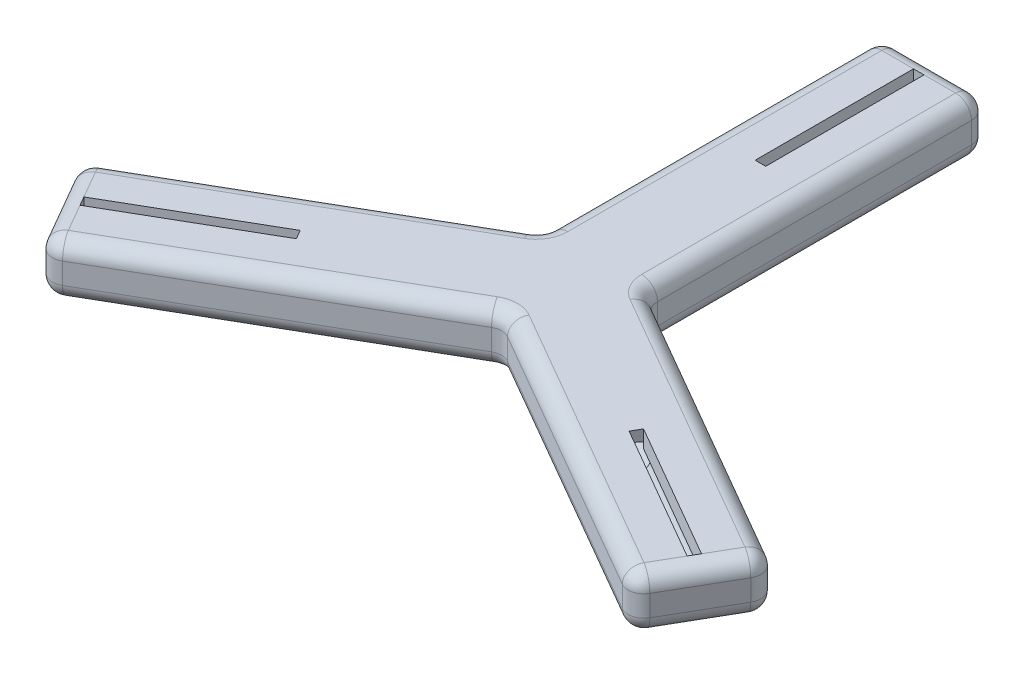
SolidWorks part; units mm, degrees
ref_plane "Front Plane" through (0, 0, 0) normal (0, 0, 1) x (1, 0, 0)
ref_plane "Top Plane" through (0, 0, 0) normal (0, 1, 0) x (1, 0, 0)
ref_plane "Right Plane" through (0, 0, 0) normal (1, 0, 0) x (0, 0, -1)
sketch "Sketch2" plane through (0, 0, 0) normal (0, 1, 0) x (1, 0, 0)
  line L3 (10, 5.7735) -> (10, 70)
  line L4 (-10, 5.7735) -> (-65.6218, -26.3397)
  line L5 (0, -11.547) -> (55.6218, -43.6603)
  line L6 (-10, 5.7735) -> (-10, 70)
  line L7 (0, -11.547) -> (-55.6218, -43.6603)
  line L8 (10, 5.7735) -> (65.6218, -26.3397)
  line L9 (-10, 70) -> (10, 70)
  line L10 (65.6218, -26.3397) -> (55.6218, -43.6603)
  line L11 (-65.6218, -26.3397) -> (-55.6218, -43.6603)
extrude "Boss-Extrude1" add sketch "Sketch2" along normal blind 10
ref_plane "Plane1" through (-2.5, 0, -4.3301) normal (-0.5, 0, -0.866) x (-0.866, 0, 0.5)
ref_plane "Plane2" through (0, 0, 0) normal (-0.5, 0, -0.866) x (-0.866, 0, 0.5)
fillet "Fillet3" radius 3 27 edges at (-10, 5, -70) (10, 5, -70) (65.6218, 5, 26.3397) (55.6218, 5, 43.6603) (-65.6218, 5, 26.3397) (-55.6218, 5, 43.6603) (10, 10, -37.8868) (10, 5, -5.7735) (37.8109, 0, 10.2831) (10, 0, -37.8868) (60.6218, 0, 35) (60.6218, 10, 35) (27.8109, 0, 27.6036) (0, 5, 11.547) (-27.8109, 0, 27.6036) (-10, 5, -5.7735) (-37.8109, 0, 10.2831) (-10, 0, -37.8868) (-60.6218, 10, 35) (-60.6218, 0, 35) (0, 0, -70) (0, 10, -70) (37.8109, 10, 10.2831) (27.8109, 10, 27.6036) (-27.8109, 10, 27.6036) (-37.8109, 10, 10.2831) (-10, 10, -37.8868)
sketch "Sketch7" plane through (0, 10, 0) normal (0, 1, 0) x (1, 0, 0)
  line L13 (-58.5364, -32.612) -> (-32.5556, -17.612)
  line L20 (57.511, -34.388) -> (31.5303, -19.388)
  line L21 (57.511, -34.388) -> (58.511, -32.6559)
  line L22 (31.5303, -19.388) -> (32.5303, -17.6559)
  line L23 (32.5303, -17.6559) -> (58.511, -32.6559)
  line L24 (-31.5556, -19.3441) -> (-57.5364, -34.3441)
  line L25 (-58.5364, -32.612) -> (-57.5364, -34.3441)
  line L26 (-32.5556, -17.612) -> (-31.5556, -19.3441)
  line L27 (1.0253, 67) -> (1.0253, 37)
  line L28 (-0.9747, 37) -> (-0.9747, 67)
  line L29 (1.0253, 67) -> (-0.9747, 67)
  line L30 (1.0253, 37) -> (-0.9747, 37)
  point P13 (0, 0)
  point P14 (0, 0)
  dimension "D1" = 2
  dimension "D3" = 30
  dimension "D2" = 3
sketch "Sketch8" plane through (60.6218, 0, 35) normal (0.866, 0, 0.5) x (0.5, 0, -0.866)
  circle A0 centre (0, 5) radius 2
  dimension "D1" = 4
extrude "Cut-Extrude8" cut sketch "Sketch8" against normal blind 33 and the other way through all
sketch "Sketch11" plane through (32.0429, 0, 18.5) normal (0.866, 0, 0.5) x (0.5, 0, -0.866)
  circle A0 centre (0, 5) radius 3
  dimension "D1" = 6
extrude "Cut-Extrude9" cut sketch "Sketch11" against normal blind 35
sketch "Sketch12" plane through (0, 0, 0) normal (0, -1, 0) x (1, 0, 0)
  circle A0 centre (0, 0) radius 0.9333
extrude "Cut-Extrude10" cut sketch "Sketch7" against normal blind 5 contours L29 L28 L30 L27
extrude "Cut-Extrude11" cut sketch "Sketch7<7>" against normal blind 5 contours L25 L26 region at (-45.046, 10, 25.9781)
sketch "Sketch7<7>" plane through (0, 10, 0) normal (0, 1, 0) x (1, 0, 0) same geometry as "Sketch7"
extrude "Cut-Extrude12" cut sketch "Sketch7<8>" against normal blind 5 contours L21 L23 region at (45.0207, 10, 26.0219)
sketch "Sketch7<8>" plane through (0, 10, 0) normal (0, 1, 0) x (1, 0, 0) same geometry as "Sketch7"
pattern_circular "CirPattern8" count 3 over 360 about axis through (0, 10, 0) along (0, 1, 0) of "Cut-Extrude8", "Cut-Extrude9"
sketch "Sketch17" plane through (60.6218, 0, 35) normal (0.866, 0, 0.5) x (0.5, 0, -0.866)
  line L0 (-7, 7) -> (-7, 3) construction
  line L1 (-7, 7) -> (7, 7)
  line L2 (-7, 7) -> (-7, 3)
  line L3 (-7, 3) -> (7, 3)
  line L4 (7, 7) -> (7, 3)
extrude "Boss-Extrude3" add sketch "Sketch17" against normal blind 3
pattern_circular "CirPattern9" count 3 over 360 about axis through (0, 10, 0) along (0, 1, 0) of "Boss-Extrude3"
